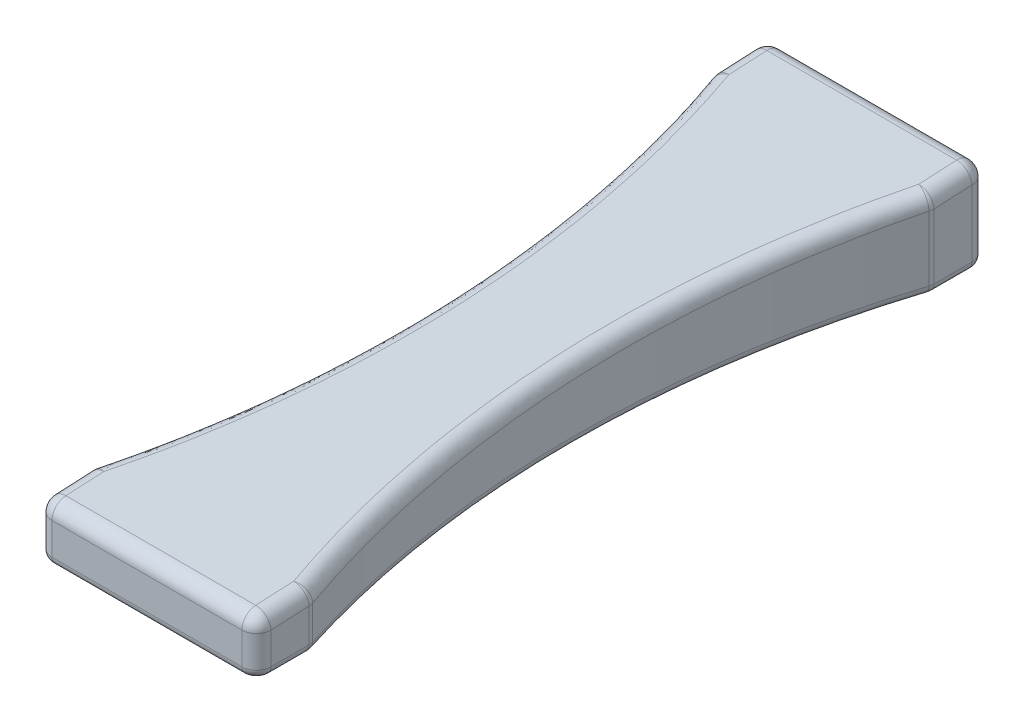
SolidWorks part; units mm, degrees
ref_plane "Front Plane" through (0, 0, 0) normal (0, 0, 1) x (1, 0, 0)
ref_plane "Top Plane" through (0, 0, 0) normal (0, 1, 0) x (1, 0, 0)
ref_plane "Right Plane" through (0, 0, 0) normal (1, 0, 0) x (0, 0, -1)
ref_plane "Plane1" through (-38.1, 0, 0) normal (-1, 0, 0) x (0, -1, 0)
sketch "Sketch1" plane through (-38.1, 0, 0) normal (-1, 0, 0) x (0, -1, 0)
  line L0 (-15.875, -127) -> (15.875, -127)
  line L1 (15.875, -127) -> (15.875, 127)
  line L2 (15.875, 127) -> (-3.175, 127)
  line L3 (-3.175, 127) -> (-15.875, -127)
extrude "Boss-Extrude1" add sketch "Sketch1" against normal blind 76.2
sketch "Sketch2" plane through (0, -15.875, 0) normal (0, -1, 0) x (1, 0, 0)
  line L0 (38.1, -107.95) -> (38.1, 107.95)
  arc A0 (38.1, 107.95) -> (38.1, -107.95) centre (376.9188, 0) ccw
extrude "Cut-Extrude1" cut sketch "Sketch2" against normal up to next
sketch "Sketch3" plane through (0, -15.875, 0) normal (0, -1, 0) x (1, 0, 0)
  line L0 (-38.1, 107.95) -> (-38.1, -107.95)
  arc A0 (-38.1, -107.95) -> (-38.1, 107.95) centre (-376.9188, 0) ccw
extrude "Cut-Extrude2" cut sketch "Sketch3" against normal up to next
fillet "Fillet1" radius 5.08 16 edges at (-38.1, 0, -127) (-38.1, 15.3988, -117.475) (-38.1, -0.4762, -107.95) (38.1, 0, -127) (0, 15.875, -127) (-21.3188, 9.525, 0) (-38.1, -5.8737, 107.95) (38.1, -0.4762, -107.95) (38.1, 15.3988, -117.475) (-38.1, 3.6513, 117.475) (-38.1, -6.35, 127) (21.3188, 9.525, 0) (38.1, -6.35, 127) (38.1, -5.8737, 107.95) (0, 3.175, 127) (38.1, 3.6513, 117.475)
fillet "Fillet2" radius 3.175 16 edges at (0, -15.875, 127) (-36.6121, -15.875, 125.5121) (36.6121, -15.875, 125.5121) (-38.1, -15.875, 115.3284) (38.1, -15.875, 115.3284) (-38.0406, -15.875, 107.962) (38.0406, -15.875, 107.962) (-21.3188, -15.875, 0) (21.3188, -15.875, 0) (-38.0406, -15.875, -107.962) (38.0406, -15.875, -107.962) (-38.1, -15.875, -115.3284) (38.1, -15.875, -115.3284) (-36.6121, -15.875, -125.5121) (36.6121, -15.875, -125.5121) (0, -15.875, -127) tangent propagation no
